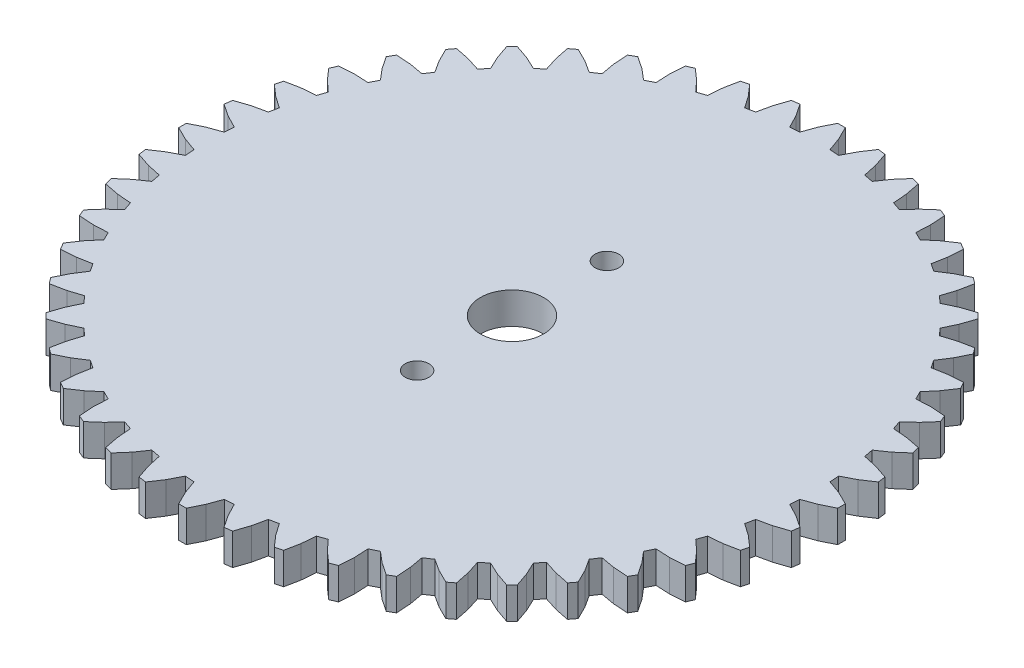
SolidWorks part; units mm, degrees
material "Acrylic (Medium-high impact)"
ref_plane "Front Plane" through (0, 0, 0) normal (0, 0, 1) x (1, 0, 0)
ref_plane "Top Plane" through (0, 0, 0) normal (0, 1, 0) x (1, 0, 0)
ref_plane "Right Plane" through (0, 0, 0) normal (1, 0, 0) x (0, 0, -1)
sketch "Sketch1" plane through (0, 0, 0) normal (0, 1, 0) x (1, 0, 0)
  line L0 (42.6708, 7.332) -> (44.3641, 6.7228)
  line L1 (44.3641, 6.7228) -> (46.0493, 5.8976)
  line L2 (46.0493, 5.8976) -> (46.0493, 4.9305)
  line L3 (46.0493, 4.9305) -> (44.3641, 4.1053)
  line L4 (44.3641, 4.1053) -> (42.6708, 3.4961)
  line L5 (42.6708, 3.4961) -> (42.5937, 2.3184)
  line L6 (42.5937, 2.3184) -> (44.1929, 1.4933)
  line L7 (44.1929, 1.4933) -> (45.7561, 0.4552)
  line L8 (45.7561, 0.4552) -> (45.6298, -0.5035)
  line L9 (45.6298, -0.5035) -> (43.8512, -1.1018)
  line L10 (43.8512, -1.1018) -> (42.093, -1.4848)
  line L11 (42.093, -1.4848) -> (41.8627, -2.6423)
  line L12 (41.8627, -2.6423) -> (43.3406, -3.669)
  line L13 (43.3406, -3.669) -> (44.7548, -4.9023)
  line L14 (44.7548, -4.9023) -> (44.5045, -5.8364)
  line L15 (44.5045, -5.8364) -> (42.663, -6.1973)
  line L16 (42.663, -6.1973) -> (40.8698, -6.3476)
  line L17 (40.8698, -6.3476) -> (40.4905, -7.4651)
  line L18 (40.4905, -7.4651) -> (41.8218, -8.676)
  line L19 (41.8218, -8.676) -> (43.0629, -10.0833)
  line L20 (43.0629, -10.0833) -> (42.6929, -10.9767)
  line L21 (42.6929, -10.9767) -> (40.82, -11.0943)
  line L22 (40.82, -11.0943) -> (39.0225, -11.0092)
  line L23 (39.0225, -11.0092) -> (38.5006, -12.0676)
  line L24 (38.5006, -12.0676) -> (39.6623, -13.4418)
  line L25 (39.6623, -13.4418) -> (40.7092, -14.9991)
  line L26 (40.7092, -14.9991) -> (40.2257, -15.8366)
  line L27 (40.2257, -15.8366) -> (38.3536, -15.7088)
  line L28 (38.3536, -15.7088) -> (36.5825, -15.3898)
  line L29 (36.5825, -15.3898) -> (35.9268, -16.371)
  line L30 (35.9268, -16.371) -> (36.8994, -17.8851)
  line L31 (36.8994, -17.8851) -> (37.734, -19.5657)
  line L32 (37.734, -19.5657) -> (37.1454, -20.3329)
  line L33 (37.1454, -20.3329) -> (35.3059, -19.9617)
  line L34 (35.3059, -19.9617) -> (33.5917, -19.4143)
  line L35 (33.5917, -19.4143) -> (32.8135, -20.3016)
  line L36 (32.8135, -20.3016) -> (33.58, -21.9296)
  line L37 (33.58, -21.9296) -> (34.1882, -23.7049)
  line L38 (34.1882, -23.7049) -> (33.5044, -24.3887)
  line L39 (33.5044, -24.3887) -> (31.7291, -23.7806)
  line L40 (31.7291, -23.7806) -> (30.1011, -23.014)
  line L41 (30.1011, -23.014) -> (29.2137, -23.7922)
  line L42 (29.2137, -23.7922) -> (29.7612, -25.5065)
  line L43 (29.7612, -25.5065) -> (30.1324, -27.3459)
  line L44 (30.1324, -27.3459) -> (29.3652, -27.9345)
  line L45 (29.3652, -27.9345) -> (27.6846, -27.0999)
  line L46 (27.6846, -27.0999) -> (26.1704, -26.1273)
  line L47 (26.1704, -26.1273) -> (25.1892, -26.783)
  line L48 (25.1892, -26.783) -> (25.5082, -28.5541)
  line L49 (25.5082, -28.5541) -> (25.6361, -30.4262)
  line L50 (25.6361, -30.4262) -> (24.7986, -30.9098)
  line L51 (24.7986, -30.9098) -> (23.2413, -29.8628)
  line L52 (23.2413, -29.8628) -> (21.8671, -28.7011)
  line L53 (21.8671, -28.7011) -> (20.8086, -29.223)
  line L54 (20.8086, -29.223) -> (20.8937, -31.0205)
  line L55 (20.8937, -31.0205) -> (20.7762, -32.8934)
  line L56 (20.7762, -32.8934) -> (19.8828, -33.2635)
  line L57 (19.8828, -33.2635) -> (18.4755, -32.0223)
  line L58 (18.4755, -32.0223) -> (17.2645, -30.691)
  line L59 (17.2645, -30.691) -> (16.147, -31.0704)
  line L60 (16.147, -31.0704) -> (15.9968, -32.8636)
  line L61 (15.9968, -32.8636) -> (15.6359, -34.7051)
  line L62 (15.6359, -34.7051) -> (14.7018, -34.9554)
  line L63 (14.7018, -34.9554) -> (13.4684, -33.5411)
  line L64 (13.4684, -33.5411) -> (12.4418, -32.0633)
  line L65 (12.4418, -32.0633) -> (11.2842, -32.2935)
  line L66 (11.2842, -32.2935) -> (10.9012, -34.0518)
  line L67 (10.9012, -34.0518) -> (10.303, -35.8303)
  line L68 (10.303, -35.8303) -> (9.3443, -35.9566)
  line L69 (9.3443, -35.9566) -> (8.3061, -34.3934)
  line L70 (8.3061, -34.3934) -> (7.4811, -32.7942)
  line L71 (7.4811, -32.7942) -> (6.3034, -32.8713)
  line L72 (6.3034, -32.8713) -> (5.6941, -34.5646)
  line L73 (5.6941, -34.5646) -> (4.869, -36.2498)
  line L74 (4.869, -36.2498) -> (3.9019, -36.2498)
  line L75 (3.9019, -36.2498) -> (3.0767, -34.5646)
  line L76 (3.0767, -34.5646) -> (2.4675, -32.8713)
  line L77 (2.4675, -32.8713) -> (1.2898, -32.7942)
  line L78 (1.2898, -32.7942) -> (0.4647, -34.3934)
  line L79 (0.4647, -34.3934) -> (-0.5735, -35.9566)
  line L80 (-0.5735, -35.9566) -> (-1.5322, -35.8303)
  line L81 (-1.5322, -35.8303) -> (-2.1304, -34.0518)
  line L82 (-2.1304, -34.0518) -> (-2.5134, -32.2935)
  line L83 (-2.5134, -32.2935) -> (-3.671, -32.0633)
  line L84 (-3.671, -32.0633) -> (-4.6976, -33.5411)
  line L85 (-4.6976, -33.5411) -> (-5.9309, -34.9554)
  line L86 (-5.9309, -34.9554) -> (-6.865, -34.7051)
  line L87 (-6.865, -34.7051) -> (-7.2259, -32.8636)
  line L88 (-7.2259, -32.8636) -> (-7.3762, -31.0704)
  line L89 (-7.3762, -31.0704) -> (-8.4937, -30.691)
  line L90 (-8.4937, -30.691) -> (-9.7047, -32.0223)
  line L91 (-9.7047, -32.0223) -> (-11.112, -33.2635)
  line L92 (-11.112, -33.2635) -> (-12.0054, -32.8934)
  line L93 (-12.0054, -32.8934) -> (-12.1229, -31.0205)
  line L94 (-12.1229, -31.0205) -> (-12.0378, -29.223)
  line L95 (-12.0378, -29.223) -> (-13.0963, -28.7011)
  line L96 (-13.0963, -28.7011) -> (-14.4705, -29.8628)
  line L97 (-14.4705, -29.8628) -> (-16.0278, -30.9098)
  line L98 (-16.0278, -30.9098) -> (-16.8653, -30.4262)
  line L99 (-16.8653, -30.4262) -> (-16.7374, -28.5541)
  line L100 (-16.7374, -28.5541) -> (-16.4184, -26.783)
  line L101 (-16.4184, -26.783) -> (-17.3996, -26.1273)
  line L102 (-17.3996, -26.1273) -> (-18.9137, -27.0999)
  line L103 (-18.9137, -27.0999) -> (-20.5944, -27.9345)
  line L104 (-20.5944, -27.9345) -> (-21.3616, -27.3459)
  line L105 (-21.3616, -27.3459) -> (-20.9903, -25.5065)
  line L106 (-20.9903, -25.5065) -> (-20.4429, -23.7922)
  line L107 (-20.4429, -23.7922) -> (-21.3303, -23.014)
  line L108 (-21.3303, -23.014) -> (-22.9583, -23.7806)
  line L109 (-22.9583, -23.7806) -> (-24.7335, -24.3887)
  line L110 (-24.7335, -24.3887) -> (-25.4174, -23.7049)
  line L111 (-25.4174, -23.7049) -> (-24.8092, -21.9296)
  line L112 (-24.8092, -21.9296) -> (-24.0427, -20.3016)
  line L113 (-24.0427, -20.3016) -> (-24.8209, -19.4143)
  line L114 (-24.8209, -19.4143) -> (-26.5351, -19.9617)
  line L115 (-26.5351, -19.9617) -> (-28.3745, -20.3329)
  line L116 (-28.3745, -20.3329) -> (-28.9632, -19.5657)
  line L117 (-28.9632, -19.5657) -> (-28.1286, -17.8851)
  line L118 (-28.1286, -17.8851) -> (-27.156, -16.371)
  line L119 (-27.156, -16.371) -> (-27.8117, -15.3898)
  line L120 (-27.8117, -15.3898) -> (-29.5827, -15.7088)
  line L121 (-29.5827, -15.7088) -> (-31.4549, -15.8366)
  line L122 (-31.4549, -15.8366) -> (-31.9384, -14.9991)
  line L123 (-31.9384, -14.9991) -> (-30.8915, -13.4418)
  line L124 (-30.8915, -13.4418) -> (-29.7297, -12.0676)
  line L125 (-29.7297, -12.0676) -> (-30.2516, -11.0092)
  line L126 (-30.2516, -11.0092) -> (-32.0492, -11.0943)
  line L127 (-32.0492, -11.0943) -> (-33.9221, -10.9767)
  line L128 (-33.9221, -10.9767) -> (-34.2921, -10.0833)
  line L129 (-34.2921, -10.0833) -> (-33.0509, -8.676)
  line L130 (-33.0509, -8.676) -> (-31.7197, -7.4651)
  line L131 (-31.7197, -7.4651) -> (-32.099, -6.3476)
  line L132 (-32.099, -6.3476) -> (-33.8922, -6.1973)
  line L133 (-33.8922, -6.1973) -> (-35.7337, -5.8364)
  line L134 (-35.7337, -5.8364) -> (-35.984, -4.9023)
  line L135 (-35.984, -4.9023) -> (-34.5698, -3.669)
  line L136 (-34.5698, -3.669) -> (-33.0919, -2.6423)
  line L137 (-33.0919, -2.6423) -> (-33.3222, -1.4848)
  line L138 (-33.3222, -1.4848) -> (-35.0804, -1.1018)
  line L139 (-35.0804, -1.1018) -> (-36.8589, -0.5035)
  line L140 (-36.8589, -0.5035) -> (-36.9853, 0.4552)
  line L141 (-36.9853, 0.4552) -> (-35.4221, 1.4933)
  line L142 (-35.4221, 1.4933) -> (-33.8228, 2.3184)
  line L143 (-33.8228, 2.3184) -> (-33.8999, 3.4961)
  line L144 (-33.8999, 3.4961) -> (-35.5933, 4.1053)
  line L145 (-35.5933, 4.1053) -> (-37.2785, 4.9305)
  line L146 (-37.2785, 4.9305) -> (-37.2785, 5.8976)
  line L147 (-37.2785, 5.8976) -> (-35.5933, 6.7228)
  line L148 (-35.5933, 6.7228) -> (-33.8999, 7.332)
  line L149 (-33.8999, 7.332) -> (-33.8228, 8.5097)
  line L150 (-33.8228, 8.5097) -> (-35.4221, 9.3348)
  line L151 (-35.4221, 9.3348) -> (-36.9853, 10.3729)
  line L152 (-36.9853, 10.3729) -> (-36.8589, 11.3316)
  line L153 (-36.8589, 11.3316) -> (-35.0804, 11.9299)
  line L154 (-35.0804, 11.9299) -> (-33.3222, 12.3129)
  line L155 (-33.3222, 12.3129) -> (-33.0919, 13.4704)
  line L156 (-33.0919, 13.4704) -> (-34.5698, 14.4971)
  line L157 (-34.5698, 14.4971) -> (-35.984, 15.7304)
  line L158 (-35.984, 15.7304) -> (-35.7337, 16.6645)
  line L159 (-35.7337, 16.6645) -> (-33.8922, 17.0254)
  line L160 (-33.8922, 17.0254) -> (-32.099, 17.1757)
  line L161 (-32.099, 17.1757) -> (-31.7197, 18.2932)
  line L162 (-31.7197, 18.2932) -> (-33.0509, 19.5041)
  line L163 (-33.0509, 19.5041) -> (-34.2921, 20.9114)
  line L164 (-34.2921, 20.9114) -> (-33.9221, 21.8048)
  line L165 (-33.9221, 21.8048) -> (-32.0492, 21.9224)
  line L166 (-32.0492, 21.9224) -> (-30.2516, 21.8373)
  line L167 (-30.2516, 21.8373) -> (-29.7297, 22.8957)
  line L168 (-29.7297, 22.8957) -> (-30.8915, 24.2699)
  line L169 (-30.8915, 24.2699) -> (-31.9384, 25.8272)
  line L170 (-31.9384, 25.8272) -> (-31.4549, 26.6647)
  line L171 (-31.4549, 26.6647) -> (-29.5827, 26.5368)
  line L172 (-29.5827, 26.5368) -> (-27.8117, 26.2178)
  line L173 (-27.8117, 26.2178) -> (-27.156, 27.1991)
  line L174 (-27.156, 27.1991) -> (-28.1286, 28.7132)
  line L175 (-28.1286, 28.7132) -> (-28.9632, 30.3938)
  line L176 (-28.9632, 30.3938) -> (-28.3745, 31.161)
  line L177 (-28.3745, 31.161) -> (-26.5351, 30.7898)
  line L178 (-26.5351, 30.7898) -> (-24.8209, 30.2424)
  line L179 (-24.8209, 30.2424) -> (-24.0427, 31.1297)
  line L180 (-24.0427, 31.1297) -> (-24.8092, 32.7577)
  line L181 (-24.8092, 32.7577) -> (-25.4174, 34.533)
  line L182 (-25.4174, 34.533) -> (-24.7335, 35.2168)
  line L183 (-24.7335, 35.2168) -> (-22.9583, 34.6087)
  line L184 (-22.9583, 34.6087) -> (-21.3303, 33.8421)
  line L185 (-21.3303, 33.8421) -> (-20.4429, 34.6203)
  line L186 (-20.4429, 34.6203) -> (-20.9903, 36.3346)
  line L187 (-20.9903, 36.3346) -> (-21.3616, 38.174)
  line L188 (-21.3616, 38.174) -> (-20.5944, 38.7626)
  line L189 (-20.5944, 38.7626) -> (-18.9137, 37.928)
  line L190 (-18.9137, 37.928) -> (-17.3996, 36.9554)
  line L191 (-17.3996, 36.9554) -> (-16.4184, 37.6111)
  line L192 (-16.4184, 37.6111) -> (-16.7374, 39.3822)
  line L193 (-16.7374, 39.3822) -> (-16.8653, 41.2543)
  line L194 (-16.8653, 41.2543) -> (-16.0278, 41.7379)
  line L195 (-16.0278, 41.7379) -> (-14.4705, 40.6909)
  line L196 (-14.4705, 40.6909) -> (-13.0963, 39.5292)
  line L197 (-13.0963, 39.5292) -> (-12.0378, 40.0511)
  line L198 (-12.0378, 40.0511) -> (-12.1229, 41.8486)
  line L199 (-12.1229, 41.8486) -> (-12.0054, 43.7215)
  line L200 (-12.0054, 43.7215) -> (-11.112, 44.0916)
  line L201 (-11.112, 44.0916) -> (-9.7047, 42.8504)
  line L202 (-9.7047, 42.8504) -> (-8.4937, 41.5191)
  line L203 (-8.4937, 41.5191) -> (-7.3762, 41.8985)
  line L204 (-7.3762, 41.8985) -> (-7.2259, 43.6917)
  line L205 (-7.2259, 43.6917) -> (-6.865, 45.5332)
  line L206 (-6.865, 45.5332) -> (-5.9309, 45.7835)
  line L207 (-5.9309, 45.7835) -> (-4.6976, 44.3692)
  line L208 (-4.6976, 44.3692) -> (-3.671, 42.8914)
  line L209 (-3.671, 42.8914) -> (-2.5134, 43.1216)
  line L210 (-2.5134, 43.1216) -> (-2.1304, 44.8799)
  line L211 (-2.1304, 44.8799) -> (-1.5322, 46.6584)
  line L212 (-1.5322, 46.6584) -> (-0.5735, 46.7847)
  line L213 (-0.5735, 46.7847) -> (0.4647, 45.2215)
  line L214 (0.4647, 45.2215) -> (1.2898, 43.6223)
  line L215 (1.2898, 43.6223) -> (2.4675, 43.6994)
  line L216 (2.4675, 43.6994) -> (3.0767, 45.3927)
  line L217 (3.0767, 45.3927) -> (3.9019, 47.0779)
  line L218 (3.9019, 47.0779) -> (4.869, 47.0779)
  line L219 (4.869, 47.0779) -> (5.6941, 45.3927)
  line L220 (5.6941, 45.3927) -> (6.3034, 43.6994)
  line L221 (6.3034, 43.6994) -> (7.4811, 43.6223)
  line L222 (7.4811, 43.6223) -> (8.3061, 45.2215)
  line L223 (8.3061, 45.2215) -> (9.3443, 46.7847)
  line L224 (9.3443, 46.7847) -> (10.303, 46.6584)
  line L225 (10.303, 46.6584) -> (10.9012, 44.8799)
  line L226 (10.9012, 44.8799) -> (11.2842, 43.1216)
  line L227 (11.2842, 43.1216) -> (12.4418, 42.8914)
  line L228 (12.4418, 42.8914) -> (13.4684, 44.3692)
  line L229 (13.4684, 44.3692) -> (14.7018, 45.7835)
  line L230 (14.7018, 45.7835) -> (15.6359, 45.5332)
  line L231 (15.6359, 45.5332) -> (15.9968, 43.6917)
  line L232 (15.9968, 43.6917) -> (16.147, 41.8985)
  line L233 (16.147, 41.8985) -> (17.2645, 41.5191)
  line L234 (17.2645, 41.5191) -> (18.4755, 42.8504)
  line L235 (18.4755, 42.8504) -> (19.8828, 44.0916)
  line L236 (19.8828, 44.0916) -> (20.7762, 43.7215)
  line L237 (20.7762, 43.7215) -> (20.8937, 41.8486)
  line L238 (20.8937, 41.8486) -> (20.8086, 40.0511)
  line L239 (20.8086, 40.0511) -> (21.8671, 39.5292)
  line L240 (21.8671, 39.5292) -> (23.2413, 40.6909)
  line L241 (23.2413, 40.6909) -> (24.7986, 41.7379)
  line L242 (24.7986, 41.7379) -> (25.6361, 41.2543)
  line L243 (25.6361, 41.2543) -> (25.5082, 39.3822)
  line L244 (25.5082, 39.3822) -> (25.1892, 37.6111)
  line L245 (25.1892, 37.6111) -> (26.1704, 36.9554)
  line L246 (26.1704, 36.9554) -> (27.6846, 37.928)
  line L247 (27.6846, 37.928) -> (29.3652, 38.7626)
  line L248 (29.3652, 38.7626) -> (30.1324, 38.174)
  line L249 (30.1324, 38.174) -> (29.7612, 36.3346)
  line L250 (29.7612, 36.3346) -> (29.2137, 34.6203)
  line L251 (29.2137, 34.6203) -> (30.1011, 33.8421)
  line L252 (30.1011, 33.8421) -> (31.7291, 34.6087)
  line L253 (31.7291, 34.6087) -> (33.5044, 35.2168)
  line L254 (33.5044, 35.2168) -> (34.1882, 34.533)
  line L255 (34.1882, 34.533) -> (33.58, 32.7577)
  line L256 (33.58, 32.7577) -> (32.8135, 31.1297)
  line L257 (32.8135, 31.1297) -> (33.5917, 30.2424)
  line L258 (33.5917, 30.2424) -> (35.3059, 30.7898)
  line L259 (35.3059, 30.7898) -> (37.1454, 31.161)
  line L260 (37.1454, 31.161) -> (37.734, 30.3938)
  line L261 (37.734, 30.3938) -> (36.8994, 28.7132)
  line L262 (36.8994, 28.7132) -> (35.9268, 27.1991)
  line L263 (35.9268, 27.1991) -> (36.5825, 26.2178)
  line L264 (36.5825, 26.2178) -> (38.3536, 26.5368)
  line L265 (38.3536, 26.5368) -> (40.2257, 26.6647)
  line L266 (40.2257, 26.6647) -> (40.7092, 25.8272)
  line L267 (40.7092, 25.8272) -> (39.6623, 24.2699)
  line L268 (39.6623, 24.2699) -> (38.5006, 22.8957)
  line L269 (38.5006, 22.8957) -> (39.0225, 21.8373)
  line L270 (39.0225, 21.8373) -> (40.82, 21.9224)
  line L271 (40.82, 21.9224) -> (42.6929, 21.8048)
  line L272 (42.6929, 21.8048) -> (43.0629, 20.9114)
  line L273 (43.0629, 20.9114) -> (41.8218, 19.5041)
  line L274 (41.8218, 19.5041) -> (40.4905, 18.2932)
  line L275 (40.4905, 18.2932) -> (40.8698, 17.1757)
  line L276 (40.8698, 17.1757) -> (42.663, 17.0254)
  line L277 (42.663, 17.0254) -> (44.5045, 16.6645)
  line L278 (44.5045, 16.6645) -> (44.7548, 15.7304)
  line L279 (44.7548, 15.7304) -> (43.3406, 14.4971)
  line L280 (43.3406, 14.4971) -> (41.8627, 13.4704)
  line L281 (41.8627, 13.4704) -> (42.093, 12.3129)
  line L282 (42.093, 12.3129) -> (43.8512, 11.9299)
  line L283 (43.8512, 11.9299) -> (45.6298, 11.3316)
  line L284 (45.6298, 11.3316) -> (45.7561, 10.3729)
  line L285 (45.7561, 10.3729) -> (44.1929, 9.3348)
  line L286 (44.1929, 9.3348) -> (42.5937, 8.5097)
  line L287 (42.5937, 8.5097) -> (42.6708, 7.332)
  line L288 (4.3854, 47.0779) -> (4.3854, -36.2498) construction
  line L289 (-37.2785, 5.414) -> (46.0493, 5.414) construction
  point P292 (4.3854, 5.414)
sketch "Sketch3" plane through (0, 0, 0) normal (0, 1, 0) x (1, 0, 0)
  line L0 (-37.2785, 5.414) -> (46.0493, 5.414) construction
  circle A0 centre (4.3854, 5.414) radius 4
  dimension "D1" = 8
sketch "Sketch4" plane through (0, 0, 0) normal (0, 1, 0) x (1, 0, 0)
  line L0 (-12.0218, 5.414) -> (22.4064, 5.414) construction
  line L1 (-37.2785, 5.414) -> (46.0493, 5.414) construction
  line L2 (4.3854, 47.0779) -> (4.3854, -36.2498) construction
  circle A0 centre (4.3854, 17.414) radius 1.5
  circle A1 centre (4.3854, -6.586) radius 1.5
  dimension "D1" = 3
  dimension "D2" = 12
extrude "Boss-Extrude2" add sketch "Sketch1" along normal blind 4
extrude "Cut-Extrude1" cut sketch "Sketch3" along normal up to next
extrude "Cut-Extrude2" cut sketch "Sketch4" along normal up to next
